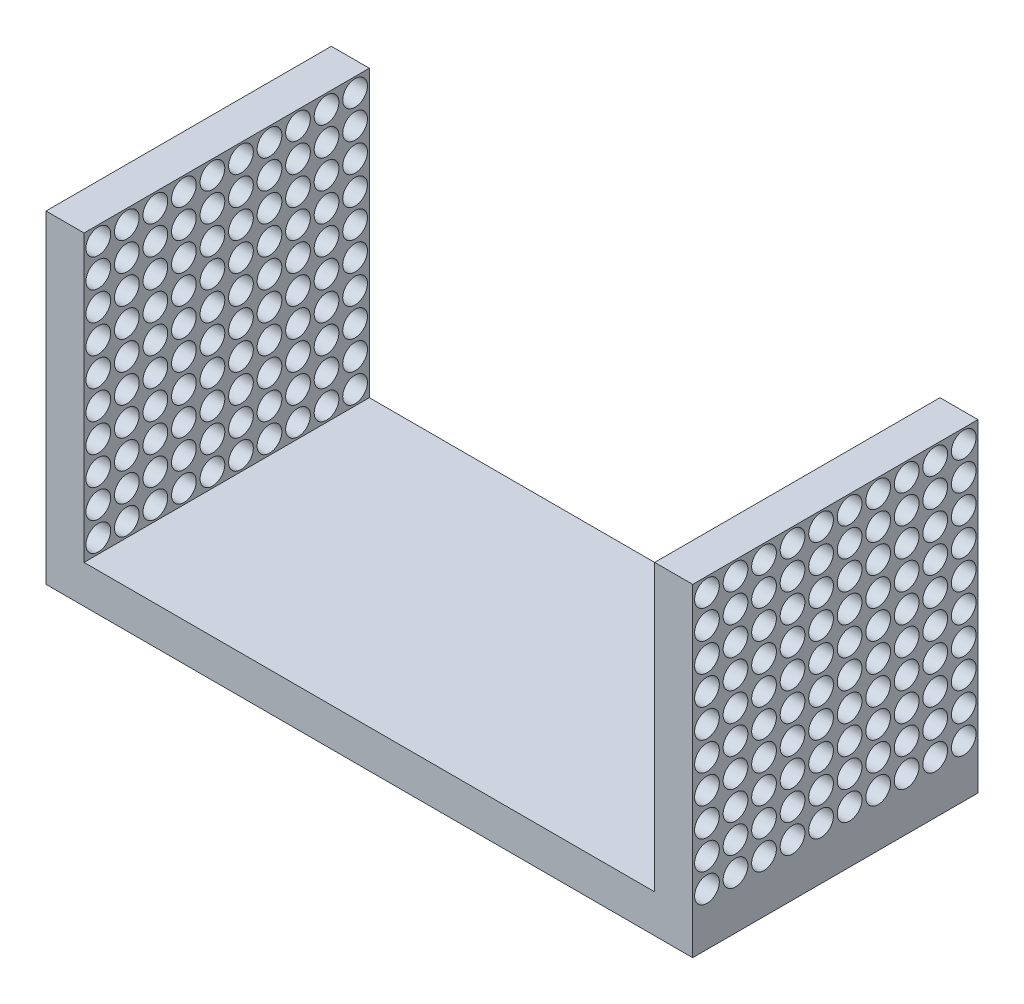
SolidWorks part; units mm, degrees
ref_plane "Front Plane" through (0, 0, 0) normal (0, 0, 1) x (1, 0, 0)
ref_plane "Top Plane" through (0, 0, 0) normal (0, 1, 0) x (1, 0, 0)
ref_plane "Right Plane" through (0, 0, 0) normal (1, 0, 0) x (0, 0, -1)
sketch "Sketch1" plane through (0, 0, 0) normal (0, 0, 1) x (1, 0, 0)
  line L1 (17, -8.5) -> (-17, -8.5)
  line L2 (17, -8.5) -> (17, 8.5)
  line L3 (17, 8.5) -> (-17, 8.5)
  line L4 (-17, -8.5) -> (-17, 8.5)
  line L5 (17, -8.5) -> (-17, 8.5) construction
  line L6 (17, 8.5) -> (-17, -8.5) construction
  point P0 (0, 0)
  dimension "D1" = 34
  dimension "D2" = 17
extrude "Boss-Extrude1" add sketch "Sketch1" along normal blind 7.5 and the other way blind 7.5
sketch "Sketch2" plane through (0, 0, 7.5) normal (0, 0, 1) x (1, 0, 0)
  line L0 (17, 8.5) -> (-17, 8.5) construction
  line L1 (15, -6.5) -> (-15, -6.5)
  line L2 (15, -6.5) -> (15, 8.5)
  line L3 (15, 8.5) -> (-15, 8.5)
  line L4 (-15, -6.5) -> (-15, 8.5)
  line L5 (15, -6.5) -> (-15, 8.5) construction
  line L6 (15, 8.5) -> (-15, -6.5) construction
  line L7 (-17, -8.5) -> (17, -8.5) construction
  line L8 (-17, 8.5) -> (-17, -8.5) construction
  line L9 (0, 1) -> (0, 0) construction
  point P0 (0, 1)
  dimension "D1" = 2
  dimension "D2" = 2
extrude "Cut-Extrude1" cut sketch "Sketch2" against normal up to surface (15 mm away) up to face at (0, 0, -7.5)
sketch "Sketch3" plane through (17, 0, 0) normal (1, 0, 0) x (0, 0, -1)
  line L0 (-6.75, 7.75) -> (-6.75, 8.5) construction
  line L1 (7.5, 8.5) -> (-7.5, 8.5) construction
  line L2 (-6.75, 7.75) -> (-7.5, 7.75) construction
  line L3 (-7.5, -8.5) -> (-7.5, 8.5) construction
  circle A0 centre (-6.75, 7.75) radius 0.65
  dimension "D3" = 1.3
  dimension "D1" = 0.75
  dimension "D2" = 0.75
extrude "Cut-Extrude2" cut sketch "Sketch3" against normal up to surface (34 mm away) up to face at (-17, 0, 0)
pattern_linear "LPattern1" count 10 spacing 1.5 along (0, 0, -1) count 10 spacing 1.5 along (0, -1, 0) of "Cut-Extrude2"
